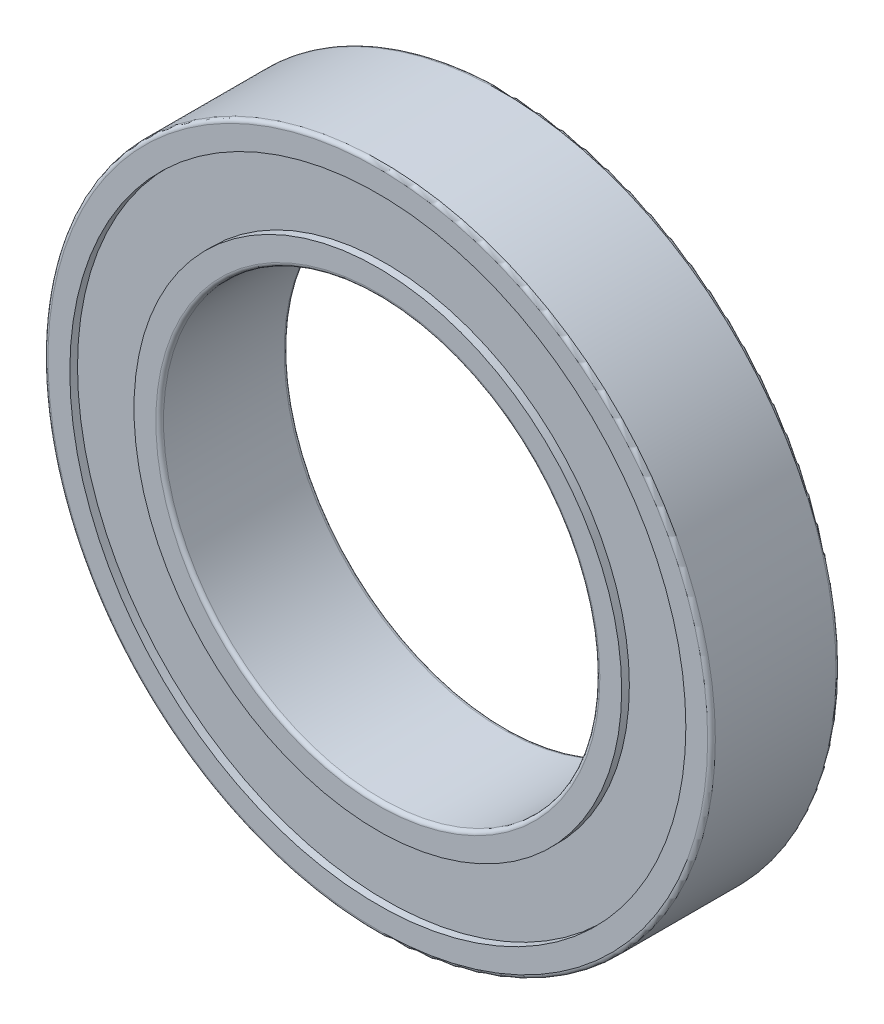
SolidWorks part; units mm, degrees
ref_plane "Front Plane" through (0, 0, 0) normal (0, 0, 1) x (1, 0, 0)
ref_plane "Top Plane" through (0, 0, 0) normal (0, 1, 0) x (1, 0, 0)
ref_plane "Right Plane" through (0, 0, 0) normal (1, 0, 0) x (0, 0, -1)
sketch "Sketch1" plane through (0, 0, 0) normal (0, 0, 1) x (1, 0, 0)
  circle A0 centre (0, 0) radius 8.5
  circle A1 centre (0, 0) radius 13
  dimension "D1" = 17
  dimension "D2" = 26
extrude "Boss-Extrude1" add sketch "Sketch1" along normal blind 5
sketch "Sketch2" plane through (0, 0, 5) normal (0, 0, 1) x (1, 0, 0)
  circle A3 centre (0, 0) radius 12
  circle A6 centre (0, 0) radius 9.5
  dimension "D1" = 24
  dimension "D2" = 19
extrude "Cut-Extrude1" cut sketch "Sketch2" against normal blind 0.3
extrude "Cut-Extrude2" cut sketch "Sketch2<2>" along normal blind 0.5 from surface starting at face at (13, 0, 0)
sketch "Sketch2<2>" plane through (0, 0, 5) normal (0, 0, 1) x (1, 0, 0) same geometry as "Sketch2"
fillet "Fillet1" radius 0.15 4 edges at (8.5, 0, 5) (13, 0, 5) (8.5, 0, 0) (13, 0, 0)
